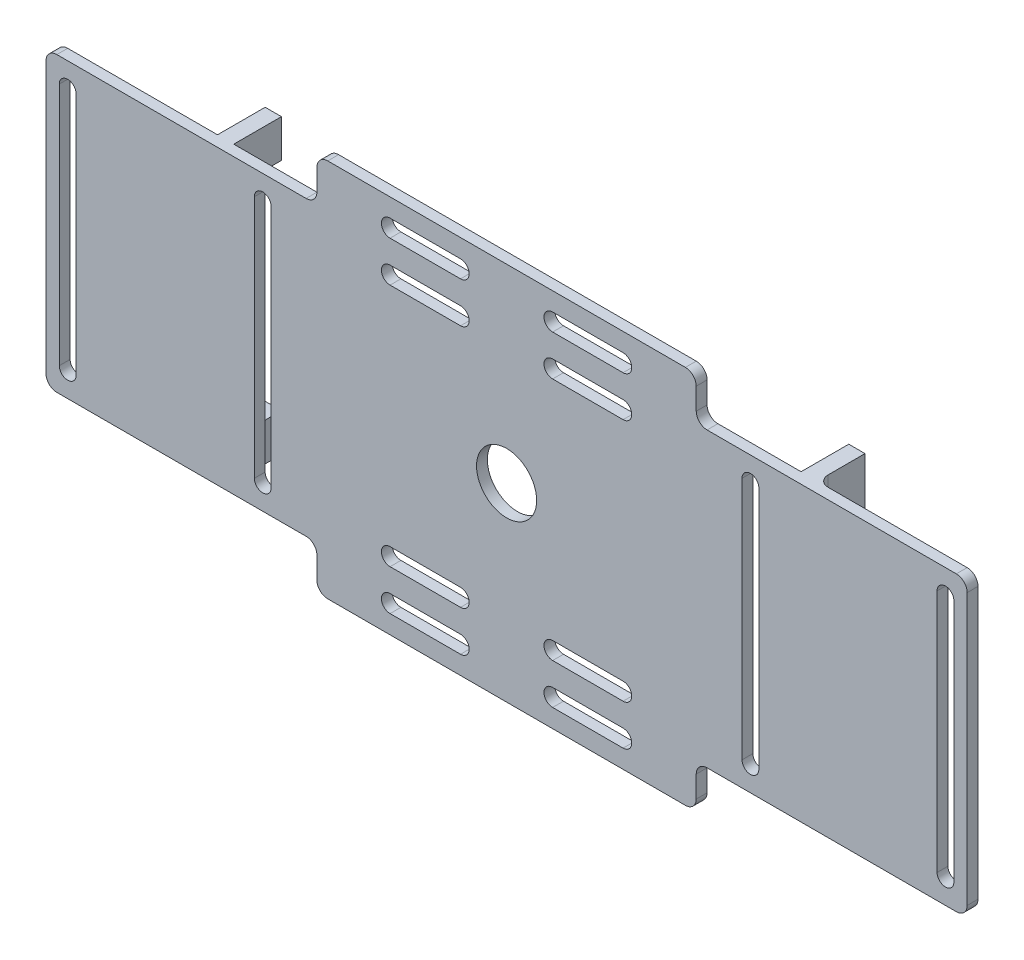
SolidWorks part; units mm, degrees
ref_plane "前基準面" through (0, 0, 0) normal (0, 0, 1) x (1, 0, 0)
ref_plane "上基準面" through (0, 0, 0) normal (0, 1, 0) x (1, 0, 0)
ref_plane "右基準面" through (0, 0, 0) normal (1, 0, 0) x (0, 0, -1)
sketch "草圖1" plane through (0, 0, 0) normal (0, 0, 1) x (1, 0, 0)
  line L1 (-85, 35) -> (85, 35)
  line L2 (-85, 35) -> (-85, -35)
  line L3 (-85, -35) -> (85, -35)
  line L4 (85, 35) -> (85, -35)
  line L5 (-85, 35) -> (85, -35) construction
  line L6 (-85, -35) -> (85, 35) construction
  point P0 (0, 0)
  dimension "D1" = 170
  dimension "D2" = 70
extrude "填料-伸長1" add sketch "草圖1" along normal blind 2
sketch "草圖2" plane through (0, 0, 2) normal (0, 0, 1) x (1, 0, 0)
  line L0 (-1000, 0) -> (49000, 0) construction
  line L1 (45, -986.1952) -> (45, 49013.8048) construction
  line L2 (-81, -962.7943) -> (-81, 49037.2057) construction
  line L3 (45, -22.5) -> (45, 22.5) construction
  line L4 (43.45, -22.5) -> (43.45, 22.5)
  line L5 (46.55, -22.5) -> (46.55, 22.5)
  line L6 (-45, -1000) -> (-45, 49000) construction
  line L7 (-45, -22.5) -> (-45, 22.5) construction
  line L8 (-46.55, -22.5) -> (-46.55, 22.5)
  line L9 (-43.45, -22.5) -> (-43.45, 22.5)
  line L10 (0, -1000) -> (0, 49000) construction
  line L11 (-1005.6924, 30) -> (48994.3076, 30) construction
  line L12 (-1002.3566, -30) -> (48997.6434, -30) construction
  line L13 (21.5, 30) -> (8.5, 30) construction
  line L16 (21.5, 28.4) -> (8.5, 28.4)
  line L19 (81, -968.4295) -> (81, 49031.5705) construction
  line L20 (-81, -22.5) -> (-81, 22.5) construction
  line L21 (-82.55, -22.5) -> (-82.55, 22.5)
  line L22 (-79.45, -22.5) -> (-79.45, 22.5)
  line L23 (81, -22.5) -> (81, 22.5) construction
  line L24 (79.45, -22.5) -> (79.45, 22.5)
  line L25 (82.55, -22.5) -> (82.55, 22.5)
  line L26 (21.5, 31.6) -> (8.5, 31.6)
  line L27 (21.5, 22.5) -> (8.5, 22.5) construction
  line L28 (21.5, 20.9) -> (8.5, 20.9)
  line L29 (21.5, 24.1) -> (8.5, 24.1)
  line L30 (-21.5, 30) -> (-8.5, 30) construction
  line L31 (-21.5, 28.4) -> (-8.5, 28.4)
  line L32 (-21.5, 31.6) -> (-8.5, 31.6)
  line L33 (-21.5, 22.5) -> (-8.5, 22.5) construction
  line L34 (-21.5, 20.9) -> (-8.5, 20.9)
  line L35 (-21.5, 24.1) -> (-8.5, 24.1)
  line L36 (21.5, -30) -> (8.5, -30) construction
  line L37 (21.5, -28.4) -> (8.5, -28.4)
  line L38 (21.5, -31.6) -> (8.5, -31.6)
  line L39 (21.5, -22.5) -> (8.5, -22.5) construction
  line L40 (21.5, -20.9) -> (8.5, -20.9)
  line L41 (21.5, -24.1) -> (8.5, -24.1)
  line L42 (-21.5, -30) -> (-8.5, -30) construction
  line L43 (-21.5, -28.4) -> (-8.5, -28.4)
  line L44 (-21.5, -31.6) -> (-8.5, -31.6)
  line L45 (-21.5, -22.5) -> (-8.5, -22.5) construction
  line L46 (-21.5, -20.9) -> (-8.5, -20.9)
  line L47 (-21.5, -24.1) -> (-8.5, -24.1)
  arc A0 (43.45, -22.5) -> (46.55, -22.5) centre (45, -22.5) ccw
  arc A1 (46.55, 22.5) -> (43.45, 22.5) centre (45, 22.5) ccw
  arc A2 (-46.55, -22.5) -> (-43.45, -22.5) centre (-45, -22.5) ccw
  arc A3 (-43.45, 22.5) -> (-46.55, 22.5) centre (-45, 22.5) ccw
  arc A12 (-82.55, -22.5) -> (-79.45, -22.5) centre (-81, -22.5) ccw
  arc A13 (-79.45, 22.5) -> (-82.55, 22.5) centre (-81, 22.5) ccw
  arc A14 (79.45, -22.5) -> (82.55, -22.5) centre (81, -22.5) ccw
  arc A15 (82.55, 22.5) -> (79.45, 22.5) centre (81, 22.5) ccw
  circle A16 centre (0, 0) radius 5.55
  arc A17 (21.5, 28.4) -> (21.5, 31.6) centre (21.5, 30) ccw
  arc A18 (8.5, 31.6) -> (8.5, 28.4) centre (8.5, 30) ccw
  arc A19 (21.5, 20.9) -> (21.5, 24.1) centre (21.5, 22.5) ccw
  arc A20 (8.5, 24.1) -> (8.5, 20.9) centre (8.5, 22.5) ccw
  arc A21 (-21.5, 28.4) -> (-21.5, 31.6) centre (-21.5, 30) cw
  arc A22 (-8.5, 31.6) -> (-8.5, 28.4) centre (-8.5, 30) cw
  arc A23 (-21.5, 20.9) -> (-21.5, 24.1) centre (-21.5, 22.5) cw
  arc A24 (-8.5, 24.1) -> (-8.5, 20.9) centre (-8.5, 22.5) cw
  arc A25 (21.5, -28.4) -> (21.5, -31.6) centre (21.5, -30) cw
  arc A26 (8.5, -31.6) -> (8.5, -28.4) centre (8.5, -30) cw
  arc A27 (21.5, -20.9) -> (21.5, -24.1) centre (21.5, -22.5) cw
  arc A28 (8.5, -24.1) -> (8.5, -20.9) centre (8.5, -22.5) cw
  arc A29 (-21.5, -28.4) -> (-21.5, -31.6) centre (-21.5, -30) ccw
  arc A30 (-8.5, -31.6) -> (-8.5, -28.4) centre (-8.5, -30) ccw
  arc A31 (-21.5, -20.9) -> (-21.5, -24.1) centre (-21.5, -22.5) ccw
  arc A32 (-8.5, -24.1) -> (-8.5, -20.9) centre (-8.5, -22.5) ccw
  point P9 (45, 0)
  point P16 (-45, 0)
  point P31 (15, 30)
  point P39 (15, 22.5)
  point P47 (-81, 0)
  point P54 (81, 0)
  point P63 (-15, 30)
  point P70 (-15, 22.5)
  point P77 (15, -30)
  point P84 (15, -22.5)
  point P91 (-15, -30)
  point P98 (-15, -22.5)
  dimension "D10" = 1.6
  dimension "D20" = 11.1
  dimension "D12" = 8.5
  dimension "D2" = 45
  dimension "D3" = 3.1
  dimension "D4" = 90
  dimension "D5" = 45
  dimension "D6" = 3.1
  dimension "D7" = 45
  dimension "D8" = 60
  dimension "D9" = 30
  dimension "D11" = 13
  dimension "D13" = 2
  dimension "D14" = 162
  dimension "D15" = 81
  dimension "D16" = 3.1
  dimension "D17" = 45
  dimension "D18" = 45
  dimension "D19" = 3.1
extrude "除料-伸長1" cut sketch "草圖2" against normal through all
sketch "草圖4" plane through (0, 0, 2) normal (0, 0, 1) x (1, 0, 0)
  line L0 (0, 52.0279) -> (0, -54.8062) construction
  line L1 (85, 35) -> (33, 35)
  line L2 (85, 35) -> (85, 25)
  line L3 (83, 27) -> (37, 27)
  line L4 (35, 33) -> (35, 29)
  line L5 (85, -35) -> (85, 35) construction
  line L6 (-98.2871, 0) -> (106.0141, 0) construction
  line L8 (35, -33) -> (35, -29)
  line L9 (83, -27) -> (37, -27)
  line L10 (85, -35) -> (85, -25)
  line L11 (85, -35) -> (33, -35)
  line L12 (-85, -35) -> (-33, -35)
  line L13 (-85, -35) -> (-85, -25)
  line L14 (-83, -27) -> (-37, -27)
  line L15 (-35, -33) -> (-35, -29)
  line L16 (-35, 33) -> (-35, 29)
  line L17 (-83, 27) -> (-37, 27)
  line L18 (-85, 35) -> (-85, 25)
  line L19 (-85, 35) -> (-33, 35)
  arc A0 (83, 27) -> (85, 25) centre (83, 25) cw
  arc A1 (37, 27) -> (35, 29) centre (37, 29) cw
  arc A2 (35, 33) -> (33, 35) centre (33, 33) ccw
  arc A3 (35, -33) -> (33, -35) centre (33, -33) cw
  arc A4 (37, -27) -> (35, -29) centre (37, -29) ccw
  arc A5 (83, -27) -> (85, -25) centre (83, -25) ccw
  arc A6 (-83, -27) -> (-85, -25) centre (-83, -25) cw
  arc A7 (-37, -27) -> (-35, -29) centre (-37, -29) cw
  arc A8 (-35, -33) -> (-33, -35) centre (-33, -33) ccw
  arc A9 (-35, 33) -> (-33, 35) centre (-33, 33) cw
  arc A10 (-37, 27) -> (-35, 29) centre (-37, 29) ccw
  arc A11 (-83, 27) -> (-85, 25) centre (-83, 25) ccw
  dimension "D1" = 2
  dimension "D2" = 2
  dimension "D3" = 2
  dimension "D4" = 52
  dimension "D5" = 8
extrude "除料-伸長2" cut sketch "草圖4" against normal through all
sketch "草圖5" plane through (0, 0, 2) normal (0, 0, 1) x (1, 0, 0)
  line L0 (0, 46.8054) -> (0, -70.1628) construction
  line L1 (-55.35, 27) -> (-52.35, 27)
  line L2 (-55.35, 27) -> (-55.35, -27)
  line L3 (-55.35, -27) -> (-52.35, -27)
  line L4 (-52.35, 27) -> (-52.35, -27)
  line L5 (52.35, 27) -> (55.35, 27)
  line L6 (52.35, 27) -> (52.35, -27)
  line L7 (52.35, -27) -> (55.35, -27)
  line L8 (55.35, 27) -> (55.35, -27)
  line L9 (-96.838, 0) -> (97.7038, 0) construction
  line L11 (-83, 27) -> (-37, 27) construction
  line L12 (-37, -27) -> (-83, -27) construction
  line L13 (83, -27) -> (37, -27) construction
  dimension "D1" = 104.7
  dimension "D2" = 3
  dimension "D3" = 3
extrude "填料-伸長2" add sketch "草圖5" against normal blind 10.8
sketch "草圖6" plane through (-55.35, 0, 0) normal (-1, 0, 0) x (0, 0, 1)
  line L0 (-21.6022, 0) -> (26.2207, 0) construction
  line L1 (-8.8, 27) -> (-8.8, -27) construction
  line L2 (-4.8, -20) -> (-8.8, -20)
  line L3 (-2.8, -18) -> (-2.8, 18)
  line L4 (-4.8, 20) -> (-8.8, 20)
  line L5 (-8.8, -20) -> (-8.8, 20)
  line L6 (-2.8, -20) -> (-8.8, 20) construction
  line L7 (-2.8, 20) -> (-8.8, -20) construction
  arc A0 (-2.8, -18) -> (-4.8, -20) centre (-4.8, -18) cw
  arc A1 (-2.8, 18) -> (-4.8, 20) centre (-4.8, 18) ccw
  point P3 (-5.8, 0)
  dimension "D3" = 2
  dimension "D4" = 2
  dimension "D1" = 6
  dimension "D2" = 40
extrude "除料-伸長3" cut sketch "草圖6" against normal up to surface (3 mm away) up to face at (-52.35, 0, -4.4)
fillet "圓角1" radius 2 1 edges at (55.35, 0, 0)
